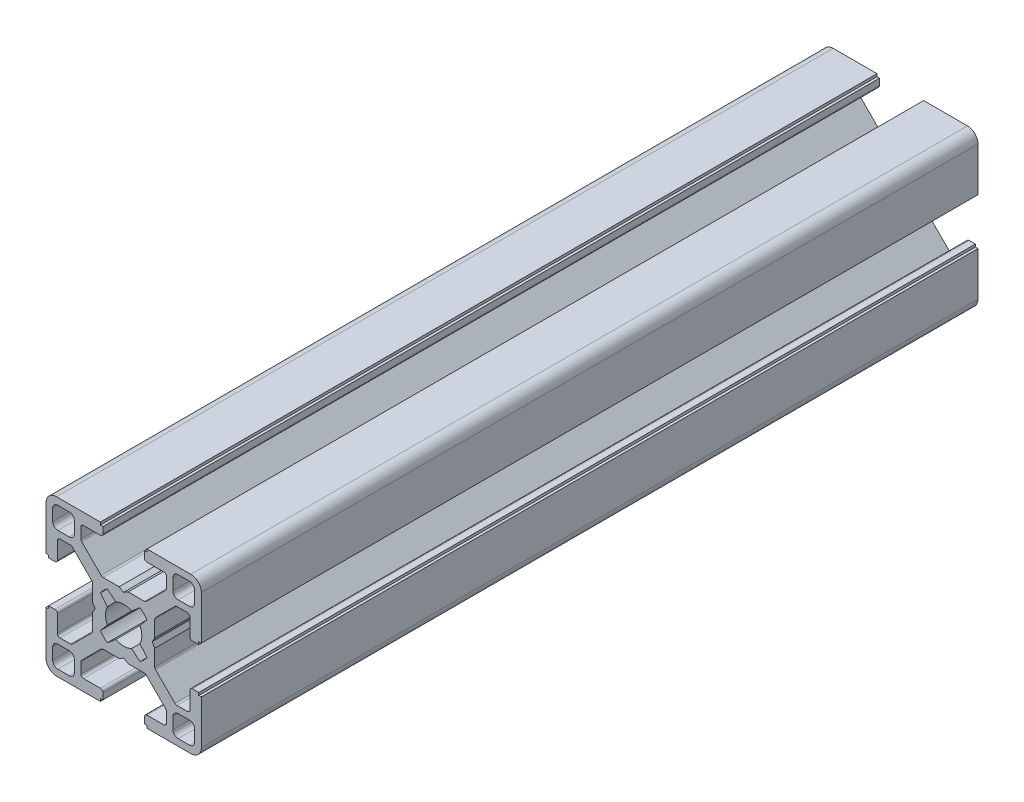
SolidWorks part; units mm, degrees
ref_plane "Front Plane" through (0, 0, 0) normal (0, 0, 1) x (1, 0, 0)
ref_plane "Top Plane" through (0, 0, 0) normal (0, 1, 0) x (1, 0, 0)
ref_plane "Right Plane" through (0, 0, 0) normal (1, 0, 0) x (0, 0, -1)
sketch "Sketch1" plane through (0, 0, 0) normal (0, 0, 1) x (1, 0, 0)
  line L0 (-15, 0) -> (15, 0) construction
  line L1 (0, -15) -> (0, 15) construction
  line L2 (-4.5, 15) -> (4.5, 15) construction
  line L3 (-4, -15) -> (4, -15) construction
  line L4 (-4.5, 15) -> (-4.5, 14.5)
  line L5 (-4.5, 14.5) -> (-4, 14.5)
  line L6 (-4, 14.5) -> (-4, 13.29)
  line L7 (-4.5, 12.79) -> (-7.7675, 12.79)
  line L8 (-8.2675, 12.29) -> (-8.2675, 10.2707)
  line L9 (-8.1211, 9.9171) -> (-4.3504, 6.1464)
  line L10 (-3.9968, 6) -> (0, 6)
  line L11 (0, 0) -> (-15, 15) construction
  line L12 (-4.5, 15) -> (-12.968, 15)
  line L14 (-12.705, 9.5135) -> (-10.5135, 9.5135)
  line L15 (-13.705, 10.5135) -> (-13.705, 12.705)
  line L16 (-12.705, 13.705) -> (-10.5135, 13.705)
  line L17 (-9.5135, 10.5135) -> (-9.5135, 12.705)
  line L18 (-13.705, 9.5135) -> (-9.5135, 13.705) construction
  line L19 (-13.705, 13.705) -> (-9.5135, 9.5135) construction
  line L20 (-3.1568, 4.5038) -> (-1.5303, 3.1477) construction
  line L21 (-4.5038, 3.1568) -> (-3.1477, 1.5303) construction
  line L22 (-6, 3.9968) -> (-6, 0)
  line L23 (-9.9171, 8.1211) -> (-6.1464, 4.3504)
  line L24 (-15, 4.5) -> (-15, 12.968)
  line L25 (-12.29, 8.2675) -> (-10.2707, 8.2675)
  line L26 (-12.79, 4.5) -> (-12.79, 7.7675)
  line L27 (-14.5, 4) -> (-13.29, 4)
  line L28 (-14.5, 4.5) -> (-14.5, 4)
  line L29 (-15, 4.5) -> (-14.5, 4.5)
  circle A0 centre (0, 0) radius 3.5
  arc A1 (-12.968, 15) -> (-15, 12.968) centre (-12.968, 12.968) ccw
  circle A2 centre (0, 0) radius 5.5 construction
  arc A3 (-10.5135, 9.5135) -> (-9.5135, 10.5135) centre (-10.5135, 10.5135) ccw
  arc A4 (-13.705, 12.705) -> (-12.705, 13.705) centre (-12.705, 12.705) cw
  arc A5 (-10.5135, 13.705) -> (-9.5135, 12.705) centre (-10.5135, 12.705) cw
  arc A6 (-12.705, 9.5135) -> (-13.705, 10.5135) centre (-12.705, 10.5135) cw
  arc A7 (-12.79, 4.5) -> (-13.29, 4) centre (-13.29, 4.5) cw
  arc A8 (-12.29, 8.2675) -> (-12.79, 7.7675) centre (-12.29, 7.7675) ccw
  arc A9 (-9.9171, 8.1211) -> (-10.2707, 8.2675) centre (-10.2707, 7.7675) ccw
  arc A10 (-6, 3.9968) -> (-6.1464, 4.3504) centre (-6.5, 3.9968) ccw
  arc A11 (-4.3504, 6.1464) -> (-3.9968, 6) centre (-3.9968, 6.5) ccw
  arc A12 (-4, 13.29) -> (-4.5, 12.79) centre (-4.5, 13.29) cw
  arc A13 (-7.7675, 12.79) -> (-8.2675, 12.29) centre (-7.7675, 12.29) ccw
  arc A14 (-8.2675, 10.2707) -> (-8.1211, 9.9171) centre (-7.7675, 10.2707) ccw
  point P4 (0, 0)
  point P8 (0, 0)
  point P13 (0, 15)
  point P15 (0, -15)
  point P16 (0, 6)
  point P23 (-11.6092, 11.6093)
  point P26 (0, 6)
  point P62 (-12.79, 4)
  point P65 (-12.79, 8.2675)
  point P68 (-10.0636, 8.2675)
  point P71 (-6, 4.2039)
  point P74 (-4.2039, 6)
  point P77 (-4, 12.79)
  point P80 (-8.2675, 12.79)
  point P83 (-8.2675, 10.0636)
  dimension "Center Hole Diameter" = 7
  dimension "D11" = 2.032
  dimension "D9" = 11
  dimension "D13" = 1
  dimension "D14" = 0.5
  dimension "Rail Height" = 30
  dimension "Rail Width" = 30
  dimension "T-Slot Width" = 8
  dimension "T-Slot Depth" = 9
  dimension "D1" = 9
  dimension "D2" = 45
  dimension "D3" = 8
  dimension "D4" = 2.21
  dimension "D5" = 16.535
  dimension "D7" = 2.54
  dimension "D6" = 1.295
  dimension "D8" = 1.246
  dimension "D10" = 10.36
  dimension "D12" = 1.905
sketch "Sketch2" plane through (0, 0, 0) normal (1, 0, 0) x (0, 0, -1)
  line L0 (-76.2, 0) -> (76.2, 0) construction
  line L2 (0, -15) -> (0, 15) construction
  line L3 (0, -15) -> (0, 15) construction
  line L4 (-76.2, -15) -> (-76.2, 15) construction
  line L5 (76.2, -15) -> (76.2, 15) construction
  point P0 (-38.7, 0)
  point P3 (0, 0)
  point P4 (38.7, 0)
  point P12 (-76.2, 0)
  point P14 (76.2, 0)
  dimension "Length" = 152.4
  dimension "D1" = 37.5
sketch "Sketch3" plane through (0, 0, 0) normal (0, 0, 1) x (1, 0, 0)
  line L0 (-4.5038, 3.1568) -> (-3.1477, 1.5303)
  line L1 (0, 3.5) -> (0, 5.5)
  line L2 (-5.5, 0) -> (-3.5, 0)
  line L7 (-6, 3.9968) -> (-6, 0) construction
  line L31 (-9.9171, 8.1211) -> (-6.1464, 4.3504) construction
  line L117 (-12.29, 8.2675) -> (-10.2707, 8.2675) construction
  line L118 (-12.79, 4.5) -> (-12.79, 7.7675) construction
  line L157 (-12.705, 9.5135) -> (-10.5135, 9.5135)
  line L158 (-9.5135, 10.5135) -> (-9.5135, 12.705)
  line L163 (-10.5135, 13.705) -> (-12.705, 13.705)
  line L164 (-13.705, 12.705) -> (-13.705, 10.5135)
  line L165 (-12.705, 9.5135) -> (-10.5135, 9.5135)
  line L166 (-9.5135, 10.5135) -> (-9.5135, 12.705)
  line L167 (-10.5135, 13.705) -> (-12.705, 13.705)
  line L168 (-13.705, 12.705) -> (-13.705, 10.5135)
  line L169 (-14.5, 4) -> (-13.29, 4) construction
  line L170 (-14.5, 4.5) -> (-14.5, 4) construction
  line L171 (-15, 4.5) -> (-14.5, 4.5) construction
  line L172 (-15, 4.5) -> (-15, 12.968) construction
  line L173 (-4.5, 15) -> (-12.968, 15) construction
  line L174 (-4.5, 15) -> (-4.5, 14.5) construction
  line L175 (-4.5, 14.5) -> (-4, 14.5) construction
  line L176 (-4, 14.5) -> (-4, 13.29) construction
  line L177 (-4.5, 12.79) -> (-7.7675, 12.79) construction
  line L178 (-8.2675, 12.29) -> (-8.2675, 10.2707) construction
  line L179 (-8.1211, 9.9171) -> (-4.3504, 6.1464) construction
  line L180 (-3.9968, 6) -> (0, 6) construction
  line L181 (-6, 3.9968) -> (-6, 0.866)
  line L182 (-9.9171, 8.1211) -> (-6.1464, 4.3504)
  line L183 (-12.29, 8.2675) -> (-10.2707, 8.2675)
  line L184 (-12.79, 4.5) -> (-12.79, 7.7675)
  line L185 (-14.5, 4) -> (-13.29, 4)
  line L186 (-14.5, 4.5) -> (-14.5, 4)
  line L187 (-15, 4.5) -> (-14.5, 4.5)
  line L188 (-15, 4.5) -> (-15, 12.968)
  line L189 (-4.5, 15) -> (-12.968, 15)
  line L190 (-4.5, 15) -> (-4.5, 14.5)
  line L191 (-4.5, 14.5) -> (-4, 14.5)
  line L192 (-4, 14.5) -> (-4, 13.29)
  line L193 (-4.5, 12.79) -> (-7.7675, 12.79)
  line L194 (-8.2675, 12.29) -> (-8.2675, 10.2707)
  line L195 (-8.1211, 9.9171) -> (-4.3504, 6.1464)
  line L196 (-3.9968, 6) -> (-0.866, 6)
  line L197 (-0.866, 6) -> (0, 5.5)
  line L198 (0, -15) -> (0, 15) construction
  line L199 (0, 0) -> (-15, 15) construction
  line L200 (0, 0) -> (-15, 15) construction
  line L201 (-3.1568, 4.5038) -> (-1.5303, 3.1477) construction
  line L202 (-3.1568, 4.5038) -> (-1.5303, 3.1477)
  line L203 (-6, 0.866) -> (-5.5, 0)
  line L204 (-15, 0) -> (15, 0) construction
  line L205 (-15, 0) -> (15, 0) construction
  line L206 (0, -15) -> (0, 15) construction
  arc A0 (-3.5, 0) -> (-3.1477, 1.5303) centre (0, 0) cw
  arc A10 (-6, 3.9968) -> (-6.1464, 4.3504) centre (-6.5, 3.9968) ccw construction
  circle A16 centre (0, 0) radius 3.5
  arc A18 (0, 3.5) -> (-1.5303, 3.1477) centre (0, 0) ccw
  arc A20 (-9.9171, 8.1211) -> (-10.2707, 8.2675) centre (-10.2707, 7.7675) ccw construction
  arc A22 (-12.29, 8.2675) -> (-12.79, 7.7675) centre (-12.29, 7.7675) ccw construction
  arc A28 (-13.29, 4) -> (-12.79, 4.5) centre (-13.29, 4.5) ccw construction
  arc A29 (-10.5135, 9.5135) -> (-9.5135, 10.5135) centre (-10.5135, 10.5135) ccw
  arc A30 (-9.5135, 12.705) -> (-10.5135, 13.705) centre (-10.5135, 12.705) ccw
  arc A31 (-12.705, 13.705) -> (-13.705, 12.705) centre (-12.705, 12.705) ccw
  arc A32 (-13.705, 10.5135) -> (-12.705, 9.5135) centre (-12.705, 10.5135) ccw
  arc A33 (-10.5135, 9.5135) -> (-9.5135, 10.5135) centre (-10.5135, 10.5135) ccw
  arc A34 (-9.5135, 12.705) -> (-10.5135, 13.705) centre (-10.5135, 12.705) ccw
  arc A35 (-12.705, 13.705) -> (-13.705, 12.705) centre (-12.705, 12.705) ccw
  arc A36 (-13.705, 10.5135) -> (-12.705, 9.5135) centre (-12.705, 10.5135) ccw
  arc A37 (-12.968, 15) -> (-15, 12.968) centre (-12.968, 12.968) ccw construction
  arc A38 (-4.5, 12.79) -> (-4, 13.29) centre (-4.5, 13.29) ccw construction
  arc A39 (-7.7675, 12.79) -> (-8.2675, 12.29) centre (-7.7675, 12.29) ccw construction
  arc A40 (-8.2675, 10.2707) -> (-8.1211, 9.9171) centre (-7.7675, 10.2707) ccw construction
  arc A41 (-4.3504, 6.1464) -> (-3.9968, 6) centre (-3.9968, 6.5) ccw construction
  arc A42 (-6, 3.9968) -> (-6.1464, 4.3504) centre (-6.5, 3.9968) ccw
  arc A43 (-9.9171, 8.1211) -> (-10.2707, 8.2675) centre (-10.2707, 7.7675) ccw
  arc A44 (-12.29, 8.2675) -> (-12.79, 7.7675) centre (-12.29, 7.7675) ccw
  arc A45 (-13.29, 4) -> (-12.79, 4.5) centre (-13.29, 4.5) ccw
  arc A46 (-12.968, 15) -> (-15, 12.968) centre (-12.968, 12.968) ccw
  arc A47 (-4.5, 12.79) -> (-4, 13.29) centre (-4.5, 13.29) ccw
  arc A48 (-7.7675, 12.79) -> (-8.2675, 12.29) centre (-7.7675, 12.29) ccw
  arc A49 (-8.2675, 10.2707) -> (-8.1211, 9.9171) centre (-7.7675, 10.2707) ccw
  arc A50 (-4.3504, 6.1464) -> (-3.9968, 6) centre (-3.9968, 6.5) ccw
  circle A51 centre (0, 0) radius 5.5 construction
  arc A52 (-3.1568, 4.5038) -> (-4.5038, 3.1568) centre (0, 0) ccw
  dimension "D3" = 60
  dimension "D4" = 60
  dimension "D1" = 0
  dimension "D2" = 0
extrude "Boss-Extrude1" add sketch "Sketch3" along normal mid plane 150
pattern_circular "CirPattern1" count 4 over 360 about axis through (0, 0, 76.2) along (0, 0, -1) of "Boss-Extrude1"
ref_plane "Contact Plane1" through (15, 0, 0) normal (1, 0, 0) x (0, 0, -1)
ref_plane "Contact Plane2" through (0, -15, 0) normal (0, 1, 0) x (1, 0, 0)
ref_plane "Contact Plane3" through (-15, 0, 0) normal (1, 0, 0) x (0, 0, -1)
ref_plane "Contact Plane4" through (0, 15, 0) normal (0, 1, 0) x (1, 0, 0)
equation "\"D1@Sketch2\" = \"Rail Height@Sketch1\" * 1.25"
equation "\"D1@Sketch1\"=\"T-Slot Width@Sketch1\"+1mm"
equation "\"D3@Sketch1\"=\"T-Slot Width@Sketch1\""
equation "\"D1@Boss-Extrude1\"=\"Width\""
equation "\"Width\"= 150mm"
